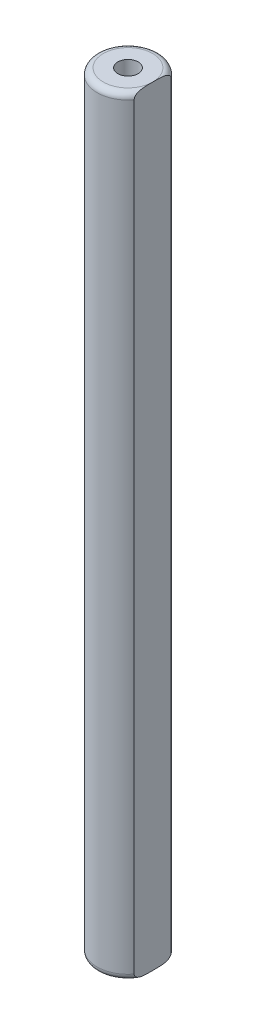
SolidWorks part; units mm, degrees
material "Alumina"
ref_plane "Front Plane" through (0, 0, 0) normal (0, 0, 1) x (1, 0, 0)
ref_plane "Top Plane" through (0, 0, 0) normal (0, 1, 0) x (1, 0, 0)
ref_plane "Right Plane" through (0, 0, 0) normal (1, 0, 0) x (0, 0, -1)
sketch "Sketch1" plane through (0, 0, 0) normal (0, 1, 0) x (1, 0, 0)
  circle A0 centre (0, 0) radius 2.5
  dimension "D1" = 5
extrude "Boss-Extrude1" add sketch "Sketch1" along normal blind 31.15
sketch "Sketch2" plane through (0, 31.15, 0) normal (0, 1, 0) x (1, 0, 0)
  circle A0 centre (0, 0) radius 0.825
  dimension "D1" = 1.65
extrude "Cut-Extrude1" cut sketch "Sketch2" against normal blind 5
sketch "Sketch3" plane through (0, 31.15, 0) normal (0, 1, 0) x (1, 0, 0)
  line L0 (2, 1.5) -> (2, -1.5)
  circle A0 centre (0, 0) radius 2.5 construction
  arc A1 (2, -1.5) -> (2, 1.5) centre (0, 0) ccw
  dimension "D1" = 3
extrude "Cut-Extrude2" cut sketch "Sketch3" against normal through all
fillet "Fillet1" radius 0.5 1 edges at (-2.5, 31.15, 0)
mirror "Mirror1" about plane through (0, 0, 0) normal (0, 1, 0) of "Fillet1", "Cut-Extrude2", "Cut-Extrude1", "Boss-Extrude1"
